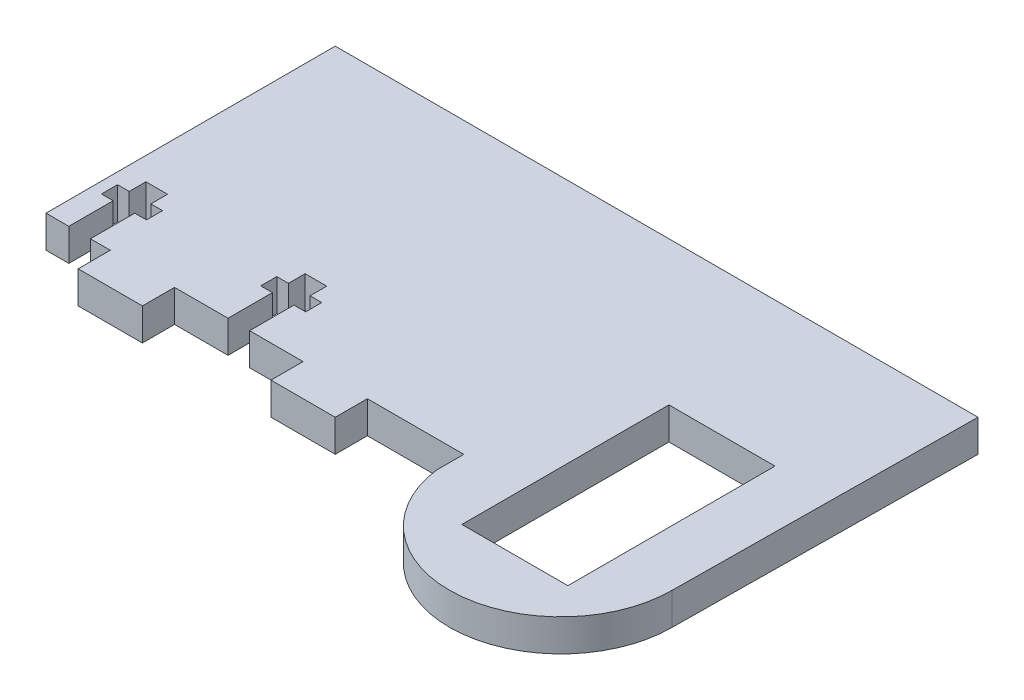
SolidWorks part; units mm, degrees
ref_plane "Front Plane" through (0, 0, 0) normal (0, 0, 1) x (1, 0, 0)
ref_plane "Top Plane" through (0, 0, 0) normal (0, 1, 0) x (1, 0, 0)
ref_plane "Right Plane" through (0, 0, 0) normal (1, 0, 0) x (0, 0, -1)
sketch "Sketch1" plane through (0, 0, 0) normal (0, 1, 0) x (1, 0, 0)
  line L0 (64.8104, 44.2474) -> (64.8104, -38.3026)
  line L1 (-62.1896, 44.2474) -> (64.8104, 44.2474)
  line L2 (-62.1896, 44.2474) -> (-62.1896, -12.9026)
  line L3 (-62.1896, -12.9026) -> (-49.4896, -12.9026)
  line L4 (-36.7896, -12.9026) -> (-11.3896, -12.9026)
  line L6 (1.3104, -12.9026) -> (1.3104, -19.2526)
  line L7 (64.8104, -38.3026) -> (20.3604, -38.3026)
  line L8 (20.3604, -12.9026) -> (20.3604, -38.3026)
  line L9 (1.3104, -19.2526) -> (-11.3896, -19.2526)
  line L10 (-11.3896, -12.9026) -> (-11.3896, -19.2526)
  line L11 (1.3104, -12.9026) -> (20.3604, -12.9026)
  line L12 (-36.7896, -12.9026) -> (-36.7896, -19.2526)
  line L13 (-36.7896, -19.2526) -> (-49.4896, -19.2526)
  line L14 (-49.4896, -12.9026) -> (-49.4896, -19.2526)
  dimension "D1" = 25.4
  dimension "D2" = 57.15
  dimension "D3" = 6.35
  dimension "D4" = 6.35
  dimension "D5" = 12.7
  dimension "D6" = 12.7
  dimension "D7" = 25.4
  dimension "D8" = 19.05
  dimension "D9" = 44.45
  dimension "D10" = 12.7
extrude "Boss-Extrude1" add sketch "Sketch1" along normal blind 6.35
sketch "Sketch4" plane through (0, 0, 0) normal (0, -1, 0) x (1, 0, 0)
  line L1 (32.1671, 25.0919) -> (53.1176, 25.0919)
  line L2 (32.1671, 25.0919) -> (32.1671, -15.8271)
  line L3 (32.1671, -15.8271) -> (53.1176, -15.8271)
  line L4 (53.1176, 25.0919) -> (53.1176, -15.8271)
extrude "Cut-Extrude2" cut sketch "Sketch4" against normal through all
sketch "Sketch6" plane through (0, 6.35, 0) normal (0, 1, 0) x (1, 0, 0)
  line L1 (-36.7896, -12.9026) -> (-11.3896, -12.9026) construction
  line L2 (-24.0896, -12.9026) -> (-24.0896, 2.4668) construction
  line B0 (-57.6823, -12.9026) -> (-53.4151, -12.9026)
  line B1 (-53.4151, -0.9646) -> (-51.1037, -0.9646)
  line B2 (-51.1037, -0.9646) -> (-51.1037, -4.1396)
  line B3 (-51.1037, -4.1396) -> (-53.4151, -4.1396)
  line B4 (-53.4151, -4.1396) -> (-53.4151, -12.9026)
  line B5 (-53.4151, -0.9646) -> (-53.4151, 2.3374)
  line B6 (-53.4151, 2.3374) -> (-57.6823, 2.3374)
  line B7 (-57.6823, -0.9646) -> (-57.6823, 2.3374)
  line B8 (-57.6823, -4.1396) -> (-57.6823, -12.9026)
  line B9 (-59.9937, -4.1396) -> (-57.6823, -4.1396)
  line B10 (-59.9937, -0.9646) -> (-59.9937, -4.1396)
  line B11 (-57.6823, -0.9646) -> (-59.9937, -0.9646)
  line B12 (-26.2232, -12.9026) -> (-21.956, -12.9026)
  line B13 (-21.956, -0.9646) -> (-19.6446, -0.9646)
  line B14 (-19.6446, -0.9646) -> (-19.6446, -4.1396)
  line B15 (-19.6446, -4.1396) -> (-21.956, -4.1396)
  line B16 (-21.956, -4.1396) -> (-21.956, -12.9026)
  line B17 (-21.956, -0.9646) -> (-21.956, 2.3374)
  line B18 (-21.956, 2.3374) -> (-26.2232, 2.3374)
  line B19 (-26.2232, -0.9646) -> (-26.2232, 2.3374)
  line B20 (-26.2232, -4.1396) -> (-26.2232, -12.9026)
  line B21 (-28.5346, -4.1396) -> (-26.2232, -4.1396)
  line B22 (-28.5346, -0.9646) -> (-28.5346, -4.1396)
  line B23 (-26.2232, -0.9646) -> (-28.5346, -0.9646)
sketch_block_instance "TSlot-1"
sketch_block "TSlot" parameters "D1"=3.302, "D2"=3.175
sketch_block_instance "TSlot-3"
extrude "Cut-Extrude4" cut sketch "Sketch6" against normal through all
sketch "Sketch7" plane through (0, 6.35, 0) normal (0, 1, 0) x (1, 0, 0)
  line L0 (20.3604, -12.9026) -> (20.3604, -38.3026)
  line L1 (20.3604, -38.3026) -> (64.8104, -38.3026)
  line L2 (64.8104, -38.3026) -> (64.8104, 44.2474)
  line L3 (64.8104, 44.2474) -> (64.2017, -15.5669)
  arc A0 (20.3604, -12.9026) -> (64.2017, -15.5669) centre (42.2001, -15.5669) ccw
  line M8 (20.3604, -38.3026) -> (64.8104, -38.3026)
  line M9 (64.8104, -38.3026) -> (64.8104, 44.2474)
extrude "Cut-Extrude5" cut sketch "Sketch7" against normal through all contours A0 L0 L3 M8 M9 region at (43.5404, 6.35, 37.6215)
